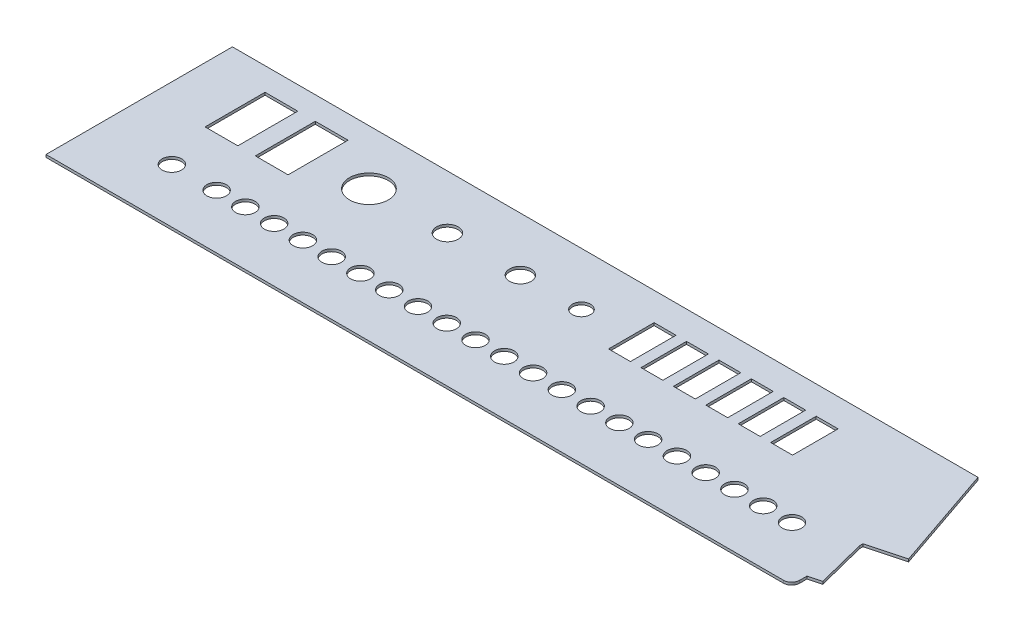
SolidWorks part; units mm, degrees
ref_plane "Front Plane" through (0, 0, 0) normal (0, 0, 1) x (1, 0, 0)
ref_plane "Top Plane" through (0, 0, 0) normal (0, 1, 0) x (1, 0, 0)
ref_plane "Right Plane" through (0, 0, 0) normal (1, 0, 0) x (0, 0, -1)
sketch "Boceto" plane through (0, 0, 0) normal (0, 1, 0) x (1, 0, 0)
  line L0 (-59.1, 30.6902) -> (-173.0029, 30.6902) construction
  line L5 (-59.1, -51.6098) -> (395.9, -51.6098) construction
  line L6 (-59.1, -51.6098) -> (-59.1, 63.3902) construction
  line L7 (-59.1, 63.3902) -> (395.9, 63.3902) construction
  line L8 (395.9, -51.6098) -> (395.9, 63.3902) construction
  line L9 (-28.6, 48.9902) -> (-8.6, 48.9902) construction
  line L10 (-28.6, 48.9902) -> (-28.6, 12.3902) construction
  line L11 (-28.6, 12.3902) -> (-8.6, 12.3902) construction
  line L12 (-8.6, 48.9902) -> (-8.6, 12.3902) construction
  line L13 (-28.6, 48.9902) -> (-8.6, 12.3902) construction
  line L14 (-28.6, 12.3902) -> (-8.6, 48.9902) construction
  line L15 (-59.1, -18.1098) -> (395.9, -18.1098) construction
  line L16 (2.4, 12.3902) -> (22.4, 12.3902) construction
  line L17 (2.4, 12.3902) -> (2.4, 48.9902) construction
  line L18 (2.4, 48.9902) -> (22.4, 48.9902) construction
  line L19 (22.4, 12.3902) -> (22.4, 48.9902) construction
  line L20 (2.4, 12.3902) -> (22.4, 48.9902) construction
  line L21 (2.4, 48.9902) -> (22.4, 12.3902) construction
  line L22 (174.9, 49.7902) -> (194.9, 49.7902) construction
  line L23 (174.9, 49.7902) -> (174.9, 11.7902) construction
  line L24 (174.9, 11.7902) -> (194.9, 11.7902) construction
  line L25 (194.9, 49.7902) -> (194.9, 11.7902) construction
  line L26 (174.9, 49.7902) -> (194.9, 11.7902) construction
  line L27 (174.9, 11.7902) -> (194.9, 49.7902) construction
  line L34 (211.4, 17.5561) -> (331, 17.5561) construction
  line L35 (211.4, 17.5561) -> (211.4, 46.5902) construction
  line L36 (211.4, 46.5902) -> (331, 46.5902) construction
  line L37 (331, 17.5561) -> (331, 46.5902) construction
  line L38 (211.4, 17.5561) -> (331, 46.5902) construction
  line L39 (211.4, 46.5902) -> (331, 17.5561) construction
  circle A0 centre (54.9, 29.6902) radius 11.1 construction
  circle A1 centre (102.75, 30.2402) radius 4.85 construction
  circle A2 centre (147.75, 30.2402) radius 4.85 construction
  circle A3 centre (-18.9, -18.1098) radius 6 construction
  circle A4 centre (8.7, -18.1098) radius 6 construction
  circle A5 centre (26.45, -18.1098) radius 6 construction
  circle A6 centre (44.2, -18.1098) radius 6 construction
  circle A7 centre (61.95, -18.1098) radius 6 construction
  circle A8 centre (79.7, -18.1098) radius 6 construction
  circle A9 centre (97.45, -18.1098) radius 6 construction
  circle A10 centre (115.2, -18.1098) radius 6 construction
  circle A11 centre (132.95, -18.1098) radius 6 construction
  circle A12 centre (150.7, -18.1098) radius 6 construction
  circle A13 centre (168.45, -18.1098) radius 6 construction
  circle A14 centre (186.2, -18.1098) radius 6 construction
  circle A15 centre (203.95, -18.1098) radius 6 construction
  circle A16 centre (221.7, -18.1098) radius 6 construction
  circle A17 centre (239.45, -18.1098) radius 6 construction
  circle A18 centre (257.2, -18.1098) radius 6 construction
  circle A19 centre (274.95, -18.1098) radius 6 construction
  circle A20 centre (292.7, -18.1098) radius 6 construction
  circle A21 centre (310.45, -18.1098) radius 6 construction
  circle A22 centre (328.2, -18.1098) radius 6 construction
  circle A23 centre (345.95, -18.1098) radius 6 construction
  circle A24 centre (363.7, -18.1098) radius 6 construction
  point P0 (0, 0)
  point P6 (-18.6, 30.6902)
  point P13 (12.4, 30.6902)
  point P24 (184.9, 30.7902)
  point P34 (271.2, 32.0731)
  dimension "D10" = 22.2
  dimension "D11" = 33.7
  dimension "D14" = 9.7
  dimension "D17" = 9.7
  dimension "D23" = 12
  dimension "D29" = 81.5
  dimension "D30" = 12
  dimension "D1" = 455
  dimension "D2" = 115
  dimension "D3" = 14.4
  dimension "D4" = 30.5
  dimension "D5" = 20
  dimension "D6" = 36.6
  dimension "D7" = 11
  dimension "D8" = 20
  dimension "D9" = 36.6
  dimension "D12" = 114
  dimension "D13" = 161.85
  dimension "D15" = 33.15
  dimension "D16" = 33.15
  dimension "D18" = 206.85
  dimension "D19" = 20
  dimension "D20" = 38
  dimension "D21" = 13.6
  dimension "D22" = 234
  dimension "D24" = 270.5
  dimension "D25" = 119.6
  dimension "D26" = 16.8
  dimension "D27" = 29.0341
  dimension "D28" = 40.2
  dimension "D31" = 27.6
  dimension "D32" = 21
sketch "Sketch4" plane through (0, 0, 0) normal (0, 1, 0) x (1, 0, 0)
  line L0 (-28.6, 48.9902) -> (-8.6, 12.3902) construction
  line L5 (-28.7093, 12.1902) -> (-8.4907, 12.1902)
  line L6 (-28.7093, 12.1902) -> (-28.7093, 49.1902)
  line L7 (-28.7093, 49.1902) -> (-8.4907, 49.1902)
  line L8 (-8.4907, 12.1902) -> (-8.4907, 49.1902)
  line L9 (-28.7093, 12.1902) -> (-8.4907, 49.1902) construction
  line L10 (-28.7093, 49.1902) -> (-8.4907, 12.1902) construction
  line L11 (-28.6, 12.3902) -> (-8.6, 48.9902) construction
  line L12 (2.4, 12.3902) -> (22.4, 48.9902) construction
  line L17 (2.2907, 12.1902) -> (2.2907, 49.1902)
  line L18 (2.2907, 12.1902) -> (22.5093, 12.1902)
  line L19 (22.5093, 12.1902) -> (22.5093, 49.1902)
  line L20 (2.2907, 49.1902) -> (22.5093, 49.1902)
  line L21 (102.75, 30.2402) -> (199.8359, 30.2402) construction
  line L22 (211.4, 32.0731) -> (331, 32.0731) construction
  line L23 (211.4, 17.5561) -> (211.4, 46.5902) construction
  line L24 (331, 17.5561) -> (331, 46.5902) construction
  line L25 (247.9, 46.1231) -> (247.9, 18.0231)
  line L26 (227.9, 46.1231) -> (214.4, 46.1231)
  line L27 (227.9, 46.1231) -> (227.9, 18.0231)
  line L28 (227.9, 18.0231) -> (214.4, 18.0231)
  line L29 (214.4, 46.1231) -> (214.4, 18.0231)
  line L30 (227.9, 46.1231) -> (214.4, 18.0231) construction
  line L31 (227.9, 18.0231) -> (214.4, 46.1231) construction
  line L32 (247.9, 46.1231) -> (234.4, 46.1231)
  line L33 (234.4, 46.1231) -> (234.4, 18.0231)
  line L34 (247.9, 18.0231) -> (234.4, 18.0231)
  line L35 (267.9, 46.1231) -> (267.9, 18.0231)
  line L36 (267.9, 46.1231) -> (254.4, 46.1231)
  line L37 (254.4, 46.1231) -> (254.4, 18.0231)
  line L38 (267.9, 18.0231) -> (254.4, 18.0231)
  line L39 (287.9, 46.1231) -> (287.9, 18.0231)
  line L40 (287.9, 46.1231) -> (274.4, 46.1231)
  line L41 (274.4, 46.1231) -> (274.4, 18.0231)
  line L42 (287.9, 18.0231) -> (274.4, 18.0231)
  line L43 (307.9, 46.1231) -> (307.9, 18.0231)
  line L44 (307.9, 46.1231) -> (294.4, 46.1231)
  line L45 (294.4, 46.1231) -> (294.4, 18.0231)
  line L46 (307.9, 18.0231) -> (294.4, 18.0231)
  line L47 (327.9, 46.1231) -> (327.9, 18.0231)
  line L48 (327.9, 46.1231) -> (314.4, 46.1231)
  line L49 (314.4, 46.1231) -> (314.4, 18.0231)
  line L50 (327.9, 18.0231) -> (314.4, 18.0231)
  line L55 (-63.0474, 63.3902) -> (-63.0474, -51.6098)
  line L59 (396.9526, -46.6098) -> (396.9526, -42.1875)
  line L60 (-63.0474, 63.3902) -> (396.9526, 63.3902)
  line L62 (-63.0474, -51.6098) -> (391.9526, -51.6098)
  line L63 (396.9526, 63.3902) -> (419.1689, -1.657)
  line L64 (419.1689, -1.657) -> (396.9526, -7.6098)
  line L65 (396.9526, -9.6098) -> (404.68, -40.1169)
  line L66 (404.68, -40.1169) -> (396.9526, -42.1875)
  line L67 (396.9526, -9.6098) -> (396.9526, -7.6098)
  circle A0 centre (54.9, 29.6902) radius 11.95
  circle A1 centre (102.75, 30.2402) radius 6.65
  circle A4 centre (147.75, 30.2402) radius 6.65
  circle A6 centre (184.9, 30.7902) radius 5.6
  circle A7 centre (-18.9, -18.1098) radius 6
  circle A8 centre (8.7, -18.1098) radius 6
  circle A9 centre (26.45, -18.1098) radius 6
  circle A10 centre (44.2, -18.1098) radius 6
  circle A11 centre (61.95, -18.1098) radius 6
  circle A12 centre (79.7, -18.1098) radius 6
  circle A13 centre (97.45, -18.1098) radius 6
  circle A14 centre (115.2, -18.1098) radius 6
  circle A15 centre (132.95, -18.1098) radius 6
  circle A16 centre (150.7, -18.1098) radius 6
  circle A17 centre (168.45, -18.1098) radius 6
  circle A18 centre (186.2, -18.1098) radius 6
  circle A19 centre (203.95, -18.1098) radius 6
  circle A20 centre (221.7, -18.1098) radius 6
  circle A21 centre (239.45, -18.1098) radius 6
  circle A22 centre (257.2, -18.1098) radius 6
  circle A23 centre (274.95, -18.1098) radius 6
  circle A24 centre (292.7, -18.1098) radius 6
  circle A25 centre (310.45, -18.1098) radius 6
  circle A26 centre (328.2, -18.1098) radius 6
  circle A27 centre (345.95, -18.1098) radius 6
  circle A28 centre (363.7, -18.1098) radius 6
  arc A30 (391.9526, -51.6098) -> (396.9526, -46.6098) centre (391.9526, -46.6098) ccw
  point P6 (-18.6, 30.6902)
  point P15 (12.4, 30.6902)
  point P40 (221.15, 32.0731)
  dimension "D3" = 23.9
  dimension "D4" = 13.3
  dimension "D5" = 2
  dimension "D6" = 11.2
  dimension "D11" = 12
  dimension "D13" = 115
  dimension "D16" = 71
  dimension "D14" = 5
  dimension "D1" = 37
  dimension "D2" = 2
  dimension "D7" = 13.5
  dimension "D8" = 28.1
  dimension "D9" = 3
  dimension "D15" = 460
  dimension "D17" = 75
  dimension "D18" = 23
  dimension "D19" = 75
  dimension "D20" = 2
  dimension "D21" = 8
  dimension "D10" = 6
  dimension "D12" = 21
extrude "Boss-Extrude3" add sketch "Sketch4" along normal blind 1.6
